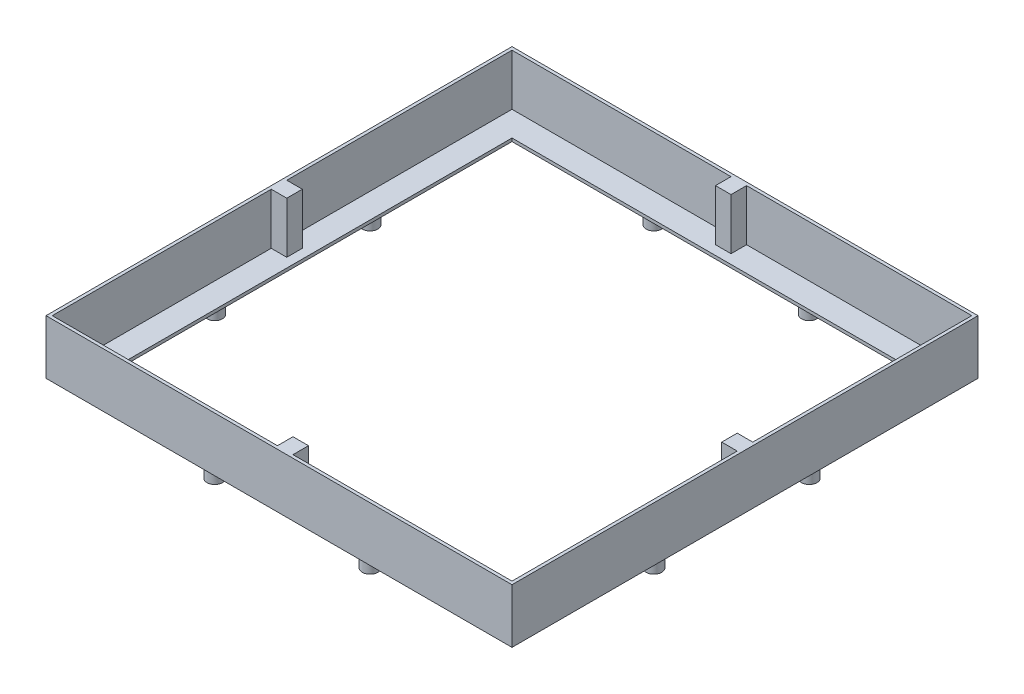
SolidWorks part; units mm, degrees
ref_plane "Front" through (0, 0, 0) normal (0, 0, 1) x (1, 0, 0)
ref_plane "Top" through (0, 0, 0) normal (0, 1, 0) x (1, 0, 0)
ref_plane "Right" through (0, 0, 0) normal (1, 0, 0) x (0, 0, -1)
sketch "Sketch1" plane through (0, 0, 0) normal (0, 1, 0) x (1, 0, 0)
  line L1 (-75, -75) -> (75, -75)
  line L2 (-75, -75) -> (-75, 75)
  line L3 (-75, 75) -> (75, 75)
  line L4 (75, -75) -> (75, 75)
  line L5 (-75, -75) -> (75, 75) construction
  line L6 (-75, 75) -> (75, -75) construction
  point P0 (0, 0)
  dimension "D1" = 150
  dimension "D2" = 150
extrude "Boss-Extrude1" add sketch "Sketch1" against normal blind 17.48
sketch "Sketch2" plane through (0, 0, 0) normal (0, 1, 0) x (1, 0, 0)
  line L1 (-74, -74) -> (74, -74)
  line L2 (-74, -74) -> (-74, 74)
  line L3 (-74, 74) -> (74, 74)
  line L4 (74, -74) -> (74, 74)
  line L5 (-74, -74) -> (74, 74) construction
  line L6 (-74, 74) -> (74, -74) construction
  point P0 (0, 0)
  dimension "D1" = 148
  dimension "D2" = 148
extrude "Cut-Extrude1" cut sketch "Sketch2" against normal blind 16.48
sketch "Sketch3" plane through (0, -16.48, 0) normal (0, 1, 0) x (1, 0, 0)
  line L1 (-66, -66) -> (66, -66)
  line L2 (-66, -66) -> (-66, 66)
  line L3 (-66, 66) -> (66, 66)
  line L4 (66, -66) -> (66, 66)
  line L5 (-66, -66) -> (66, 66) construction
  line L6 (-66, 66) -> (66, -66) construction
  point P0 (0, 0)
  dimension "D1" = 132
  dimension "D2" = 132
extrude "Cut-Extrude2" cut sketch "Sketch3" against normal through all
sketch "Sketch4" plane through (0, 0, -74) normal (0, 0, 1) x (1, 0, 0)
  line L3 (74, 0) -> (-74, 0) construction
  line L4 (-3.5, -17.47) -> (1.5, -17.47)
  line L5 (-3.5, -17.47) -> (-3.5, 0)
  line L6 (-3.5, 0) -> (1.5, 0)
  line L7 (1.5, -17.47) -> (1.5, 0)
  line L8 (-3.5, -17.47) -> (1.5, 0) construction
  line L9 (-3.5, 0) -> (1.5, -17.47) construction
  point P6 (-1, -8.735)
  dimension "D1" = 5
extrude "Boss-Extrude3" add sketch "Sketch4" along normal blind 5
ref_axis "Axis1" through (0, 0, 0) along (0, 1, 0)
pattern_circular "CirPattern2" count 4 over 360 about axis through (0, 0, 0) along (0, 1, 0) of "Boss-Extrude3"
sketch "Sketch6" plane through (0, -17.48, 0) normal (0, -1, 0) x (1, 0, 0)
  line L0 (75, -75) -> (-75, -75) construction
  line L1 (-75, 75) -> (75, 75) construction
  circle A0 centre (-70.6782, -25) radius 2.5
  circle A1 centre (-70.6782, 25) radius 2.5
  circle A2 centre (25, 70.6782) radius 2.5
  circle A3 centre (-25, 70.6782) radius 2.5
  circle A4 centre (70.6782, -25) radius 2.5
  circle A5 centre (70.6782, 25) radius 2.5
  circle A6 centre (-25, -70.6782) radius 2.5
  circle A7 centre (25, -70.6782) radius 2.5
  dimension "D1" = 5
  dimension "D3" = 5
  dimension "D2" = 50
  dimension "D4" = 50
  dimension "D5" = 4
extrude "Boss-Extrude5" add sketch "Sketch6" along normal blind 5
